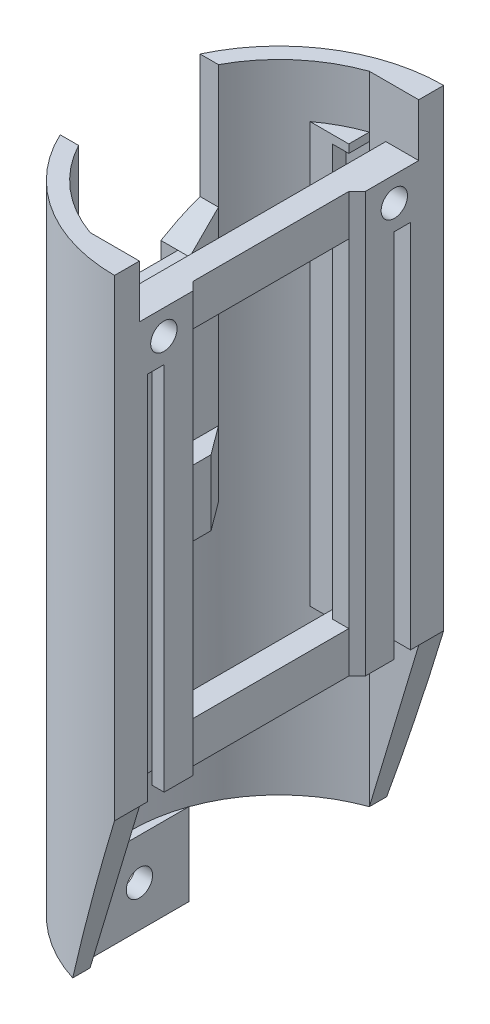
SolidWorks part; units mm, degrees
ref_plane "前视基准面" through (0, 0, 0) normal (0, 0, 1) x (1, 0, 0)
ref_plane "上视基准面" through (0, 0, 0) normal (0, 1, 0) x (1, 0, 0)
ref_plane "右视基准面" through (0, 0, 0) normal (1, 0, 0) x (0, 0, -1)
other "Configuration Table"
sketch "草图1" plane through (0, 0, 0) normal (0, 1, 0) x (1, 0, 0)
  line L0 (0, -473.638) -> (0, 23208.2609) construction
  line L1 (0, 0) -> (-4, 0) construction
  line L2 (0, 20) -> (0, -20)
  line L3 (-4, -17.5499) -> (-4, 17.5499)
  arc A0 (0, 20) -> (0, -20) centre (0, 0) ccw
  arc A1 (-4, 17.5499) -> (-4, -17.5499) centre (0, 0) ccw
  point P12 (-4, 0)
  dimension "D1" = 40
  dimension "D2" = 36
  dimension "D3" = 4
extrude "凸台-拉伸1" add sketch "草图1" along normal blind 70
sketch "草图3" plane through (0, 0, 0) normal (1, 0, 0) x (0, 0, -1)
  line L0 (-20, 0) -> (20, 0) construction
  line L1 (-16, 60) -> (16, 60) construction
  line L2 (-16, 60) -> (-16, 0) construction
  line L3 (-16, 0) -> (16, 0) construction
  line L4 (16, 60) -> (16, 0) construction
  line L5 (-20, 70) -> (20, 70) construction
  circle A0 centre (-14, 58) radius 2 construction
  circle A1 centre (14, 58) radius 2 construction
  circle A2 centre (-14, 58) radius 1
  circle A3 centre (14, 58) radius 1
  point P4 (0, 60)
  dimension "D4" = 4
  dimension "D5" = 4
  dimension "D6" = 2
  dimension "D7" = 2
  dimension "D1" = 0
  dimension "D2" = 10
  dimension "D3" = 32
extrude "切除-拉伸2" cut sketch "草图3" against normal up to surface (4 mm away) from surface up to face at (-4, 35, 0) starting at face at (0, 35, 0)
sketch "草图5" plane through (0, 0, 0) normal (0, 1, 0) x (1, 0, 0)
  line L0 (0, -1000) -> (0, 49000) construction
  line L1 (-1000, 0) -> (49000, 0) construction
  line L2 (-6, 16.9706) -> (6, 16.9706) construction
  line L3 (-6, -16.9706) -> (6, -16.9706) construction
  line L4 (0, 16.9706) -> (0, -16.9706)
  line L5 (0, -16.9706) -> (-4, -16.9706)
  line L6 (-4, -17.5499) -> (-4, 17.5499) construction
  line L7 (-4, -16.9706) -> (-4, 16.9706)
  line L8 (-4, 16.9706) -> (0, 16.9706)
  circle A0 centre (0, 0) radius 18 construction
  point P11 (0, 16.9706)
  dimension "D1" = 12
extrude "切除-拉伸4" cut sketch "草图5" against normal blind 9 from surface starting at face at (-10, 70, 0)
sketch "草图6" plane through (0, 0, 0) normal (0, 1, 0) x (1, 0, 0)
  line L0 (-4, 16.9706) -> (-6, 16.9706)
  line L1 (0, 16.9706) -> (0, 18)
  line L2 (-4, -16.9706) -> (-6, -16.9706)
  line L3 (0, -16.9706) -> (0, -18)
  line L4 (-4, 16.9706) -> (-4, -16.9706)
  line L5 (0, 16.9706) -> (-4, 16.9706)
  line L6 (0, -16.9706) -> (0, 16.9706)
  line L7 (-4, -16.9706) -> (0, -16.9706)
  line L9 (0, 16.9706) -> (-4, 16.9706)
  line L11 (-4, -16.9706) -> (0, -16.9706)
  arc A0 (0, 18) -> (-6, 16.9706) centre (0, 0) ccw
  arc A1 (-6, -16.9706) -> (0, -18) centre (0, 0) ccw
  dimension "D1" = 0
extrude "凸台-拉伸2" add sketch "草图6" against normal up to surface from surface up to face at (-10, 0, 0) starting at face at (-6.25, 70, 0)
sketch "草图7" plane through (0, 0, 0) normal (0, 1, 0) x (1, 0, 0)
  line L4 (-4, 16.9706) -> (-4, -16.9706)
  line L5 (0, 16.9706) -> (-4, 16.9706)
  line L6 (0, -16.9706) -> (0, 16.9706)
  line L7 (-4, -16.9706) -> (0, -16.9706)
  line L8 (-4, 16.9706) -> (-4, -16.9706)
  line L9 (0, 16.9706) -> (-4, 16.9706)
  line L10 (0, -16.9706) -> (0, 16.9706)
  line L11 (-4, -16.9706) -> (0, -16.9706)
  dimension "D1" = 0
extrude "切除-拉伸5" cut sketch "草图7" along normal blind 10
sketch "草图8" plane through (0, 0, 0) normal (0, 1, 0) x (1, 0, 0)
  line L0 (0, 16.9706) -> (0, -16.9706) construction
  line L1 (-6, 16.9706) -> (0, 16.9706)
  line L2 (-6, 16.9706) -> (-6, 14.4706)
  line L3 (-6, 14.4706) -> (0, 14.4706)
  line L4 (0, 16.9706) -> (0, 14.4706)
  line L6 (0, -16.9706) -> (-6, -16.9706)
  line L7 (0, -16.9706) -> (0, -14.4706)
  line L8 (0, -14.4706) -> (-6, -14.4706)
  line L9 (-6, -16.9706) -> (-6, -14.4706)
  dimension "D1" = 2.5
  dimension "D2" = 2.5
extrude "凸台-拉伸3" add sketch "草图8" against normal blind 1 from surface starting at face at (-2, 61, 0)
sketch "草图10" plane through (0, 0, 0) normal (0, 1, 0) x (1, 0, 0)
  line L0 (-6, 16.9706) -> (-6, 14.4706)
  line L1 (-6, 14.4706) -> (-10.7053, 14.4706)
  line L2 (-6, -14.4706) -> (-10.7053, -14.4706)
  line L3 (-6, -14.4706) -> (-6, -16.9706)
  arc A0 (-6, 16.9706) -> (-10.7053, 14.4706) centre (0, 0) ccw
  arc A1 (-10.7053, -14.4706) -> (-6, -16.9706) centre (0, 0) ccw
extrude "凸台-拉伸4" add sketch "草图10" along normal up to surface (70 mm away) from surface up to face at (-7.3333, 70, 0) starting at face at (-7.3333, 0, 0)
sketch "草图11" plane through (0, 0, 0) normal (0, 1, 0) x (1, 0, 0)
  line L0 (0, 16.9706) -> (0, -16.9706) construction
  line L1 (-6, 16.9706) -> (0, 16.9706)
  line L2 (-6, 16.9706) -> (-6, 14.4706)
  line L3 (-6, 14.4706) -> (0, 14.4706)
  line L4 (0, 16.9706) -> (0, 14.4706)
  line L5 (-6, 14.4706) -> (-10.7053, 14.4706) construction
  line L7 (-6, -14.4706) -> (0, -14.4706)
  line L8 (-6, -14.4706) -> (-6, -16.9706)
  line L9 (-6, -16.9706) -> (0, -16.9706)
  line L10 (0, -14.4706) -> (0, -16.9706)
  dimension "D1" = 0
extrude "凸台-拉伸5" add sketch "草图11" along normal up to surface (70 mm away) from surface up to face at (-7.2705, 70, 0) starting at face at (-4, 61, 0)
sketch "草图12" plane through (0, 0, 0) normal (0, 0, 1) x (1, 0, 0)
  line L1 (-6, 60) -> (-4, 60)
  line L2 (-6, 60) -> (-6, 61)
  line L3 (-6, 61) -> (-4, 61)
  line L4 (-4, 60) -> (-4, 61)
extrude "切除-拉伸6" cut sketch "草图12" against normal up to surface (16.9706 mm away) from surface up to face at (-3.3333, 23.3333, -16.9706) starting at face at (-3.3333, 23.3333, 16.9706)
sketch "草图14" plane through (0, 0, 0) normal (0, 1, 0) x (1, 0, 0)
  line L0 (-4, -14.4706) -> (-4, 14.4706) construction
  line L1 (-4, 10.4706) -> (-3, 10.4706)
  line L2 (-4, 10.4706) -> (-4, -10.4706)
  line L3 (-4, -10.4706) -> (-3, -10.4706)
  line L4 (-3, 10.4706) -> (-3, -10.4706)
  line L5 (-10.7053, -14.4706) -> (0, -14.4706) construction
  line L6 (-4, 14.4706) -> (0, 14.4706) construction
  line L7 (0, 14.4706) -> (0, -14.4706) construction
  line L8 (-1, 10.4706) -> (0, 10.4706)
  line L9 (-1, 10.4706) -> (-1, -10.4706)
  line L10 (-1, -10.4706) -> (0, -10.4706)
  line L11 (0, 10.4706) -> (0, -10.4706)
  line L12 (0, -14.4706) -> (-4, -14.4706) construction
  line L13 (0, 14.4706) -> (-10.7053, 14.4706) construction
  dimension "D1" = 1
  dimension "D2" = 4
  dimension "D3" = 4
  dimension "D4" = 1
  dimension "D5" = 4
  dimension "D6" = 4
extrude "切除-拉伸8" cut sketch "草图14" along normal up to surface (61 mm away) from surface up to face at (-2, 61, 0) starting at face at (-2, 10, 0)
sketch "草图15" plane through (0, 0, 0) normal (1, 0, 0) x (0, 0, -1)
  line L0 (10.4706, 61) -> (10.4706, 10) construction
  line L5 (-10.4706, 61) -> (-10.4706, 10) construction
  line L6 (10.4706, 61) -> (-10.4706, 61) construction
  line L7 (-10.4706, 10) -> (10.4706, 10) construction
  line L9 (-9.4706, 56) -> (9.4706, 56)
  line L10 (-9.4706, 56) -> (-9.4706, 15)
  line L11 (-9.4706, 15) -> (9.4706, 15)
  line L12 (9.4706, 56) -> (9.4706, 15)
  dimension "D1" = 1
  dimension "D2" = 1
  dimension "D3" = 5
  dimension "D4" = 5
extrude "切除-拉伸9" cut sketch "草图15" against normal up to surface (3 mm away) from surface up to face at (-3, 35.5, 0) starting at face at (-1, 35.5, 0)
sketch "草图17" plane through (0, 0, 0) normal (1, 0, 0) x (0, 0, -1)
  circle A0 centre (-14, 58) radius 1.6
  circle A1 centre (14, 58) radius 1.6
  dimension "D1" = 3.2
  dimension "D2" = 3.2
extrude "切除-拉伸10" cut sketch "草图17" against normal blind 2.5
sketch "草图20" plane through (0, 0, 0) normal (0, 1, 0) x (1, 0, 0)
  line L0 (-1, 10.4706) -> (0, 10.4706)
  line L1 (0, 14.4706) -> (0, 10.4706) construction
  line L2 (0, 10.4706) -> (-1, 10.4706) construction
  line L3 (0, 10.4706) -> (-1, 9.4706)
  line L4 (-1, 10.4706) -> (-1, -10.4706) construction
  line L5 (-1, 9.4706) -> (-1, 10.4706)
  line L6 (-4, 10.4706) -> (-3, 10.4706)
  line L7 (-3, 10.4706) -> (-3, 9.4706)
  line L8 (-3, -10.4706) -> (-3, 10.4706) construction
  line L9 (-3, 9.4706) -> (-4, 10.4706)
  line L10 (-4, -10.4706) -> (-3, -10.4706)
  line L11 (-3, -10.4706) -> (-3, -9.4706)
  line L12 (-3, -9.4706) -> (-4, -10.4706)
  line L13 (0, -10.4706) -> (-1, -10.4706)
  line L14 (-1, -10.4706) -> (0, -10.4706) construction
  line L15 (-1, -10.4706) -> (-1, -9.4706)
  line L16 (-1, -9.4706) -> (0, -10.4706)
  dimension "D1" = 1
  dimension "D2" = 1
  dimension "D3" = 1
  dimension "D4" = 1
  dimension "D5" = 1
extrude "凸台-拉伸11" add sketch "草图20" against normal up to surface (-10 mm away) from surface up to face at (-2, 10, 0) starting at face at (-2, 61, 0)
sketch "草图21" plane through (0, 0, 0) normal (0, 1, 0) x (1, 0, 0)
  line L0 (-4, 10.4706) -> (-4, -10.4706)
  line L1 (-4, -10.4706) -> (-3, -9.4706)
  line L2 (-3, -9.4706) -> (-3, 9.4706)
  line L3 (-3, 9.4706) -> (-4, 10.4706)
extrude "凸台-拉伸12" add sketch "草图21" against normal up to surface (-56 mm away) from surface up to face at (-2, 56, 0) starting at face at (-2, 61, 0)
sketch "草图22" plane through (0, 0, 0) normal (0, 1, 0) x (1, 0, 0)
  line L4 (-4, 10.4706) -> (-4, -10.4706)
  line L5 (-4, -10.4706) -> (-3, -9.4706)
  line L6 (-3, -9.4706) -> (-3, 9.4706)
  line L7 (-3, 9.4706) -> (-4, 10.4706)
  line L8 (-4, 10.4706) -> (-4, -10.4706)
  line L9 (-4, -10.4706) -> (-3, -9.4706)
  line L10 (-3, -9.4706) -> (-3, 9.4706)
  line L11 (-3, 9.4706) -> (-4, 10.4706)
  dimension "D1" = 0
extrude "凸台-拉伸13" add sketch "草图22" along normal up to surface (15 mm away) from surface up to face at (-2, 15, 0) starting at face at (-2, 10, 0)
sketch "草图23" plane through (0, 0, 0) normal (0, 0, 1) x (1, 0, 0)
  line L0 (-3, 56) -> (-1, 56) construction
  line L1 (-6, 61) -> (-8, 61)
  line L2 (-6, 61) -> (-6, 55)
  line L3 (-6, 55) -> (-8, 55)
  line L4 (-8, 61) -> (-8, 55)
  dimension "D1" = 1
  dimension "D2" = 2
extrude "切除-拉伸11" cut sketch "草图23" along normal up to surface (1.654 mm away) from surface up to face at (-14.3526, 35, 0) starting at face at (-5.3444, 46.1429, 14.4706)
sketch "草图24" plane through (0, 0, 0) normal (0, 0, 1) x (1, 0, 0)
  line L4 (-6, 61) -> (-8, 61)
  line L5 (-8, 61) -> (-8, 55)
  line L6 (-8, 55) -> (-6, 55)
  line L7 (-6, 55) -> (-6, 61)
  line L8 (-6, 61) -> (-8, 61)
  line L9 (-8, 61) -> (-8, 55)
  line L10 (-8, 55) -> (-6, 55)
  line L11 (-6, 55) -> (-6, 61)
  dimension "D1" = 0
extrude "切除-拉伸12" cut sketch "草图24" against normal up to surface (16.1245 mm away) up to face at (-14.3526, 35, 0)
sketch "草图25" plane through (0, 0, 0) normal (0, 1, 0) x (1, 0, 0)
  line L0 (-6, -16.9706) -> (-6, -14.4706)
  line L1 (-8, -14.4706) -> (-4, -14.4706) construction
  line L2 (-6, -14.4706) -> (-10.7053, -14.4706)
  line L3 (-10.7053, 14.4706) -> (-6, 14.4706)
  line L4 (-4, 14.4706) -> (-8, 14.4706) construction
  line L5 (-6, 14.4706) -> (-6, 16.9706)
  arc A0 (-10.7053, -14.4706) -> (-6, -16.9706) centre (0, 0) ccw
  arc A1 (-6, 16.9706) -> (-10.7053, 14.4706) centre (0, 0) ccw
extrude "切除-拉伸13" cut sketch "草图25" along normal up to surface (10 mm away) from surface up to face at (-1.25, 10, 0) starting at face at (-7.2705, 0, 0)
sketch "草图29" plane through (0, 0, 0) normal (0, 1, 0) x (1, 0, 0)
  line L0 (0, -16.9706) -> (0, -14.4706)
  line L1 (0, -14.4706) -> (-10.7053, -14.4706)
  line L2 (0, -16.9706) -> (-6, -16.9706)
  line L3 (-4, -16.9706) -> (-6, -16.9706)
  line L4 (0, -18) -> (0, -16.9706)
  line L5 (0, -16.9706) -> (-4, -16.9706)
  line L6 (-4, -16.9706) -> (-6, -16.9706) construction
  line L8 (0, -16.9706) -> (-4, -16.9706) construction
  line L9 (-6, 16.9706) -> (-4, 16.9706)
  line L10 (0, 16.9706) -> (0, 18)
  line L11 (-4, 16.9706) -> (0, 16.9706)
  line L12 (-6, 16.9706) -> (-4, 16.9706) construction
  line L14 (-4, 16.9706) -> (0, 16.9706) construction
  line L15 (-6, 16.9706) -> (0, 16.9706)
  line L16 (0, 16.9706) -> (0, 14.4706)
  line L17 (0, 14.4706) -> (-10.7053, 14.4706)
  arc A0 (-10.7053, -14.4706) -> (-6, -16.9706) centre (0, 0) ccw
  arc A1 (-6, -16.9706) -> (0, -18) centre (0, 0) ccw
  arc A3 (0, 18) -> (-6, 16.9706) centre (0, 0) ccw
  arc A5 (-6, 16.9706) -> (-10.7053, 14.4706) centre (0, 0) ccw
  dimension "D1" = 0
  dimension "D2" = 0
extrude "切除-拉伸18" cut sketch "草图29" against normal up to surface (-61 mm away) from surface up to face at (-1.25, 61, 0) starting at face at (-8.1175, 70, 0)
sketch "草图30" plane through (0, 0, 0) normal (0, 1, 0) x (1, 0, 0)
  line L0 (-8, 16.1245) -> (-8, 14.4706)
  line L1 (-8, 14.4706) -> (-4, 14.4706)
  line L2 (-4, -16.9706) -> (-4, 16.9706) construction
  line L3 (-4, 14.4706) -> (-4, 16.9706)
  line L4 (-6, 16.9706) -> (0, 16.9706) construction
  line L5 (-4, 16.9706) -> (-6, 16.9706)
  line L6 (-8, -16.1245) -> (-8, -14.4706)
  line L7 (-8, -14.4706) -> (-4, -14.4706)
  line L8 (-4, -14.4706) -> (-4, -16.9706)
  line L9 (-4, -16.9706) -> (-6, -16.9706)
  arc A0 (-6, 16.9706) -> (-8, 16.1245) centre (0, 0) ccw
  arc A1 (-8, -16.1245) -> (-6, -16.9706) centre (0, 0) ccw
extrude "凸台-拉伸16" add sketch "草图30" against normal blind 1 from surface starting at face at (-8.9139, 61, -15.0418)
sketch "草图31" plane through (0, 0, 0) normal (0, 1, 0) x (1, 0, 0)
  line L4 (0, -20) -> (0, -16.9706)
  line L5 (0, -16.9706) -> (-6, -16.9706)
  line L6 (-6, 16.9706) -> (0, 16.9706)
  line L7 (0, 16.9706) -> (0, 20)
  line L8 (0, -20) -> (0, -16.9706)
  line L9 (0, -16.9706) -> (-6, -16.9706)
  line L10 (-6, 16.9706) -> (0, 16.9706)
  line L11 (0, 16.9706) -> (0, 20)
  arc A2 (-6, 16.9706) -> (-6, -16.9706) centre (0, 0) ccw
  arc A3 (0, 20) -> (0, -20) centre (0, 0) ccw
  arc A4 (-6, 16.9706) -> (-6, -16.9706) centre (0, 0) ccw
  arc A5 (0, 20) -> (0, -20) centre (0, 0) ccw
  dimension "D1" = 0
extrude "凸台-拉伸17" add sketch "草图31" along normal blind 2.4 from surface starting at face at (-7.3333, 70, 0)
sketch "草图32" plane through (0, 0, 0) normal (0, 1, 0) x (1, 0, 0)
  line L4 (0, 16.9706) -> (0, 20)
  line L5 (0, -20) -> (0, -16.9706)
  line L6 (0, -16.9706) -> (-6, -16.9706)
  line L7 (-6, 16.9706) -> (0, 16.9706)
  line L8 (0, 16.9706) -> (0, 20)
  line L9 (0, -20) -> (0, -16.9706)
  line L10 (0, -16.9706) -> (-6, -16.9706)
  line L11 (-6, 16.9706) -> (0, 16.9706)
  arc A2 (0, 20) -> (0, -20) centre (0, 0) ccw
  arc A3 (-6, 16.9706) -> (-6, -16.9706) centre (0, 0) ccw
  arc A4 (0, 20) -> (0, -20) centre (0, 0) ccw
  arc A5 (-6, 16.9706) -> (-6, -16.9706) centre (0, 0) ccw
  dimension "D1" = 0
extrude "切除-拉伸19" cut sketch "草图32" against normal blind 5 from surface starting at face at (-7.3333, 72.4, 0)
sketch "草图33" plane through (0, 0, 0) normal (0, 1, 0) x (1, 0, 0)
  line L0 (-1000, 0) -> (49000, 0) construction
  line L1 (-17.2916, -5) -> (-17.2916, 5)
  line L2 (-17.2916, 5) -> (-19.3649, 5)
  line L3 (-17.2916, -5) -> (-19.3649, -5)
  arc A0 (-17.2916, 5) -> (-17.2916, -5) centre (0, 0) ccw construction
  arc A1 (-19.3649, 5) -> (-19.3649, -5) centre (0, 0) ccw
  point P11 (-17.2916, 0)
  dimension "D1" = 10
extrude "切除-拉伸20" cut sketch "草图33" against normal blind 45 from surface starting at face at (-7.3333, 67.4, 0)
sketch "草图39" plane through (0, 0, 0) normal (0, 1, 0) x (1, 0, 0)
  line L0 (-20, 0) -> (-15.8666, 0) construction
  line L1 (-15.8666, -8.5) -> (-15.8666, 8.5)
  line L2 (-15.8666, 8.5) -> (-18.1039, 8.5)
  line L3 (-15.8666, -8.5) -> (-18.1039, -8.5)
  arc A0 (-18.1039, 8.5) -> (-18.1039, -8.5) centre (0, 0) ccw
  arc A1 (-15.8666, 8.5) -> (-15.8666, -8.5) centre (0, 0) ccw construction
  point P11 (-15.8666, 0)
  dimension "D1" = 17
extrude "切除-拉伸22" cut sketch "草图39" against normal blind 15 from surface contours L2 A0 L3 L1 region at (-17.6683, 0, 0) starting at face at (-9.3339, 67.4, 13.7237)
sketch "草图40" plane through (0, 0, 0) normal (1, 0, 0) x (0, 0, -1)
  line L0 (-5, 52.4) -> (-8.5, 52.4)
  line L1 (-8.5, 52.4) -> (-5, 48.9)
  line L2 (-5, 22.4) -> (-5, 52.4) construction
  line L3 (-5, 48.9) -> (-5, 52.4)
  line L4 (8.5, 52.4) -> (5, 52.4)
  line L5 (5, 52.4) -> (5, 48.9)
  line L6 (5, 22.4) -> (5, 52.4) construction
  line L7 (5, 48.9) -> (8.5, 52.4)
  dimension "D1" = 3.5
  dimension "D2" = 3.5
extrude "切除-拉伸25" cut sketch "草图40" against normal through all
sketch "草图41" plane through (0, 0, 0) normal (0, 1, 0) x (1, 0, 0)
  line L0 (-1000, 0) -> (49000, 0) construction
  line L1 (-15.8666, 8.5) -> (-15.8666, -8.5)
  line L2 (-17.2916, 5) -> (-17.2916, -5)
  arc A0 (-17.2916, -5) -> (-15.8666, -8.5) centre (0, 0) ccw
  arc A1 (-15.8666, 8.5) -> (-17.2916, 5) centre (0, 0) ccw
extrude "凸台-拉伸24" add sketch "草图41" along normal up to vertex (48.9 mm away) from surface up to point (-19.3649, 48.9, -5) starting at face at (-18.6641, 22.4, 0)
sketch "草图42" plane through (0, 0, 0) normal (1, 0, 0) x (0, 0, -1)
  line L0 (-8.5, 52.4) -> (-8.5, 48.9)
  line L1 (-8.5, 48.9) -> (-5, 48.9)
  line L2 (-5, 48.9) -> (-8.5, 52.4)
  line L3 (8.5, 52.4) -> (8.5, 48.9)
  line L4 (8.5, 48.9) -> (5, 48.9)
  line L5 (5, 48.9) -> (8.5, 52.4)
extrude "凸台-拉伸25" add sketch "草图42" against normal up to surface (2.2372 mm away) from surface up to face at (-14.5014, 43.0882, 0) starting at face at (-15.8666, 35.65, 0)
sketch "草图43" plane through (0, 0, 0) normal (0, 1, 0) x (1, 0, 0)
  line L0 (-15.8666, 8.5) -> (-15.8666, -8.5)
  arc A0 (-15.8666, 8.5) -> (-15.8666, -8.5) centre (0, 0) ccw
extrude "凸台-拉伸26" add sketch "草图43" against normal blind 1 from surface starting at face at (-16.6252, 22.4, 0)
sketch "草图44" plane through (0, 0, 0) normal (0, 1, 0) x (1, 0, 0)
  line L0 (-1000, 0) -> (49000, 0) construction
  line L1 (-15.8666, 0) -> (-13.2666, 0) construction
  line L2 (-15.8666, 5) -> (-15.8666, -5) construction
  line L3 (-13.2666, -5) -> (-13.2666, 5)
  line L4 (-13.2666, 5) -> (-15.8666, 8.5)
  line L5 (-13.2666, -5) -> (-15.8666, -8.5)
  line L6 (-15.8666, 8.5) -> (-15.8666, -8.5)
  circle A1 centre (0, 0) radius 18 construction
  point P12 (-13.2666, 0)
  dimension "D1" = 2.6
  dimension "D2" = 10
extrude "凸台-拉伸27" add sketch "草图44" along normal blind 8 from surface starting at face at (-16.9333, 21.4, 0)
sketch "草图45" plane through (0, 0, 0) normal (1, 0, 0) x (0, 0, -1)
  line L0 (0, 67.4) -> (0, 21.4) construction
  line L2 (5, 22.4) -> (-5, 22.4) construction
  circle A0 centre (0, 26.4) radius 1
  dimension "D1" = 2
  dimension "D2" = 4
extrude "切除-拉伸26" cut sketch "草图45" along normal up to surface (-13.2666 mm away) from surface up to face at (-13.2666, 25.4, 0) starting at face at (-17.2916, 35.65, 0)
sketch "草图46" plane through (0, 0, 0) normal (0, 1, 0) x (1, 0, 0)
  line L0 (-15.8666, 5) -> (-15.8666, -5) construction
  line L1 (-15.8666, 2) -> (-14.2666, 2)
  line L2 (-15.8666, 2) -> (-15.8666, -2)
  line L3 (-15.8666, -2) -> (-14.2666, -2)
  line L4 (-14.2666, 2) -> (-14.2666, -2)
  line L5 (-17.2916, -5) -> (-17.2916, 5) construction
  point P8 (-17.2916, 0)
  point P9 (-15.8666, 0)
  dimension "D1" = 4
  dimension "D2" = 1.6
extrude "切除-拉伸27" cut sketch "草图46" along normal blind 5 from surface starting at face at (-15.1, 21.4, 0)
sketch "草图47" plane through (0, 0, 0) normal (1, 0, 0) x (0, 0, -1)
  line L1 (0, 24.0906) -> (2, 25.2453)
  line L2 (2, 25.2453) -> (2, 27.5547)
  line L3 (2, 27.5547) -> (0, 28.7094)
  line L4 (0, 28.7094) -> (-2, 27.5547)
  line L5 (-2, 27.5547) -> (-2, 25.2453)
  line L6 (-2, 25.2453) -> (0, 24.0906)
  circle A0 centre (0, 26.4) radius 2 construction
  dimension "D1" = 4
extrude "切除-拉伸28" cut sketch "草图47" against normal up to surface (15.8666 mm away) from surface up to face at (-15.8666, 24.5667, 0) starting at face at (-14.2666, 24.5667, 0)
sketch "草图48" plane through (0, 0, 0) normal (1, 0, 0) x (0, 0, -1)
  line L0 (5, 22.4) -> (3, 22.4)
  line L1 (5, 22.4) -> (-5, 22.4) construction
  line L2 (3, 22.4) -> (5, 24.4)
  line L3 (5, 22.4) -> (5, 48.9) construction
  line L4 (5, 24.4) -> (5, 22.4)
  line L5 (-5, 22.4) -> (-5, 24.4)
  line L6 (-5, 22.4) -> (-5, 48.9) construction
  line L7 (-5, 24.4) -> (-3, 22.4)
  line L8 (-3, 22.4) -> (-5, 22.4)
  dimension "D1" = 2
  dimension "D2" = 2
  dimension "D3" = 2
  dimension "D4" = 2
extrude "凸台-拉伸28" add sketch "草图48" against normal up to surface (2.0733 mm away) from surface up to face at (-14.5014, 43.0882, 0) starting at face at (-17.2916, 26.4, 1)
sketch "草图49" plane through (0, 0, 0) normal (0, 1, 0) x (1, 0, 0)
  line L1 (-6, -16.9706) -> (-4, -16.9706)
  line L2 (-6, -16.9706) -> (-6, 16.9706)
  line L3 (-6, 16.9706) -> (-4, 16.9706)
  line L4 (-4, -16.9706) -> (-4, 16.9706)
extrude "切除-拉伸29" cut sketch "草图49" along normal through all
sketch "草图50" plane through (0, 0, 0) normal (0, 1, 0) x (1, 0, 0)
  line L0 (0, 16.9706) -> (0, 15.9706) construction
  line L1 (0, 16.9706) -> (0, 10.4706) construction
  line L2 (0, 15.9706) -> (-3, 15.9706)
  line L3 (-3, 15.9706) -> (-3, 11.9706)
  line L4 (-3, 11.9706) -> (-1.5, 11.9706)
  line L5 (-1.5, 11.9706) -> (-1.5, 13.9706)
  line L6 (-1.5, 13.9706) -> (0, 13.9706)
  line L7 (-1000, 0) -> (49000, 0) construction
  line L8 (-1.5, -13.9706) -> (0, -13.9706)
  line L9 (-1.5, -11.9706) -> (-1.5, -13.9706)
  line L10 (-3, -11.9706) -> (-1.5, -11.9706)
  line L11 (-3, -15.9706) -> (-3, -11.9706)
  line L12 (0, -15.9706) -> (-3, -15.9706)
  line L13 (0, -16.9706) -> (0, -15.9706) construction
  line L14 (0, 15.9706) -> (0, 13.9706)
  line L15 (0, -13.9706) -> (0, -15.9706)
  dimension "D1" = 1
  dimension "D2" = 3
  dimension "D3" = 1.5
  dimension "D4" = 2
  dimension "D5" = 2
extrude "切除-拉伸30" cut sketch "草图50" along normal blind 45 from surface starting at face at (-1.25, 10, 0)
sketch "草图51" plane through (0, 0, 0) normal (0, 1, 0) x (1, 0, 0)
  line L0 (0, -11.9706) -> (3, -11.9706)
  line L1 (0, -13.9706) -> (0, -10.4706) construction
  line L2 (3, -11.9706) -> (3, -14.9706)
  line L3 (3, -14.9706) -> (0, -14.9706) construction
  line L4 (1.5, -14.9706) -> (1.5, -13.9706)
  line L5 (1.5, -13.9706) -> (0, -13.9706)
  line L6 (-3, -11.9706) -> (-1.5, -11.9706) construction
  line L7 (1.5, -14.9706) -> (3, -14.9706)
  line L8 (0, -13.9706) -> (0, -11.9706)
  line L9 (-1000, 0) -> (49000, 0) construction
  line L10 (3, 14.9706) -> (0, 14.9706) construction
  line L11 (0, 13.9706) -> (0, 11.9706)
  line L12 (1.5, 14.9706) -> (3, 14.9706)
  line L13 (1.5, 13.9706) -> (0, 13.9706)
  line L14 (1.5, 14.9706) -> (1.5, 13.9706)
  line L15 (3, 11.9706) -> (3, 14.9706)
  line L16 (0, 11.9706) -> (3, 11.9706)
  dimension "D1" = 3
  dimension "D2" = 3
  dimension "D3" = 3
extrude "凸台-拉伸29" add sketch "草图51" along normal blind 45 from surface starting at face at (-1.4, 10, 0)
sketch "草图52" plane through (0, 0, 0) normal (0, 1, 0) x (1, 0, 0)
  line L4 (0, -16.9706) -> (-6, -16.9706)
  line L5 (0, -20) -> (0, -16.9706)
  line L6 (0, 16.9706) -> (0, 20)
  line L7 (-6, 16.9706) -> (0, 16.9706)
  line L8 (0, -16.9706) -> (-6, -16.9706)
  line L9 (0, -20) -> (0, -16.9706)
  line L10 (0, 16.9706) -> (0, 20)
  line L11 (-6, 16.9706) -> (0, 16.9706)
  arc A2 (-6, 16.9706) -> (-6, -16.9706) centre (0, 0) ccw
  arc A3 (0, 20) -> (0, -20) centre (0, 0) ccw
  arc A4 (-6, 16.9706) -> (-6, -16.9706) centre (0, 0) ccw
  arc A5 (0, 20) -> (0, -20) centre (0, 0) ccw
  dimension "D1" = 0
extrude "凸台-拉伸30" add sketch "草图52" against normal blind 10
sketch "草图58" plane through (0, 0, 0) normal (0, 1, 0) x (1, 0, 0)
  line L0 (1.5, -13.9706) -> (1.5, -14.9706) construction
  line L1 (1.5, -14.9706) -> (3, -14.9706) construction
  line L2 (3, -14.9706) -> (3, -11.9706) construction
  line L3 (3, -11.9706) -> (0, -11.9706) construction
  line L4 (0, -11.9706) -> (0, -13.9706) construction
  line L5 (0, -13.9706) -> (1.5, -13.9706) construction
  line L6 (1.5, 13.9706) -> (0, 13.9706) construction
  line L7 (0, 13.9706) -> (0, 11.9706) construction
  line L8 (0, 11.9706) -> (3, 11.9706) construction
  line L9 (3, 11.9706) -> (3, 14.9706) construction
  line L10 (3, 14.9706) -> (1.5, 14.9706) construction
  line L11 (1.5, 14.9706) -> (1.5, 13.9706) construction
  line L12 (1.5, -13.9706) -> (1.5, -14.9706)
  line L13 (1.5, -14.9706) -> (3, -14.9706)
  line L14 (3, -14.9706) -> (3, -11.9706)
  line L15 (3, -11.9706) -> (0, -11.9706)
  line L16 (0, -11.9706) -> (0, -13.9706)
  line L17 (0, -13.9706) -> (1.5, -13.9706)
  line L18 (1.5, 13.9706) -> (0, 13.9706)
  line L19 (0, 13.9706) -> (0, 11.9706)
  line L20 (0, 11.9706) -> (3, 11.9706)
  line L21 (3, 11.9706) -> (3, 14.9706)
  line L22 (3, 14.9706) -> (1.5, 14.9706)
  line L23 (1.5, 14.9706) -> (1.5, 13.9706)
extrude "切除-拉伸34" cut sketch "草图58" along normal up to surface (55 mm away) from surface up to face at (1.5, 55, 13.6372) starting at face at (-0.3571, 10, 0)
sketch "草图60" plane through (0, 0, 0) normal (0, 0, 1) x (1, 0, 0)
  line L0 (0, 10) -> (-6, -10)
  line L1 (-6, -10) -> (0, -10)
  line L2 (0, -10) -> (0, 10)
extrude "切除-拉伸35" cut sketch "草图60" against normal through all and the other way through all
sketch "草图61" plane through (0, 0, 0) normal (0, 1, 0) x (1, 0, 0)
  line L0 (-1000, 0) -> (49000, 0) construction
  line L1 (-16.9706, 6) -> (-16.9706, -6)
  line L2 (-16.9706, -6) -> (-19.0788, -6)
  line L3 (-16.9706, 6) -> (-19.0788, 6)
  arc A0 (-19.0788, 6) -> (-19.0788, -6) centre (0, 0) ccw
  arc A1 (-16.9706, 6) -> (-16.9706, -6) centre (0, 0) ccw construction
  point P11 (-16.9706, 0)
  dimension "D1" = 12
extrude "凸台-拉伸32" add sketch "草图61" against normal blind 10 from surface starting at face at (-12.5, -10, 0)
sketch "草图62" plane through (0, 0, 0) normal (0, 1, 0) x (1, 0, 0)
  line L0 (-19.0788, -6) -> (-19.0788, 6)
  arc A0 (-19.0788, 6) -> (-19.0788, -6) centre (0, 0) ccw construction
  arc A1 (-19.0788, 6) -> (-19.0788, -6) centre (0, 0) ccw
extrude "切除-拉伸36" cut sketch "草图62" against normal blind 10 from surface starting at face at (-12.7237, -10, 12.7237)
sketch "草图63" plane through (0, 0, 0) normal (1, 0, 0) x (0, 0, -1)
  line L0 (-6, -20) -> (6, -20) construction
  line L1 (6, -20) -> (6, -10) construction
  circle A0 centre (0, -15) radius 1.6
  dimension "D1" = 3.2
  dimension "D2" = 5
  dimension "D3" = 6
extrude "切除-拉伸37" cut sketch "草图63" against normal through all
sketch "草图65" plane through (0, 0, 0) normal (1, 0, 0) x (0, 0, -1)
  line L0 (-6, -10) -> (6, -10)
  line L3 (6, -10) -> (6, -14)
  line L11 (6, -20) -> (6, -10) construction
  line L12 (6, -14) -> (3, -11)
  line L13 (3, -11) -> (-3, -11)
  line L14 (-3, -11) -> (-6, -14)
  line L15 (-6, -20) -> (-6, -10) construction
  line L16 (-6, -14) -> (-6, -10)
  point P14 (12.0034, -11.9994)
  dimension "D1" = 4
  dimension "D2" = 6
  dimension "D3" = 3
  dimension "D4" = 4
  dimension "D5" = 3
extrude "凸台-拉伸33" add sketch "草图65" against normal up to surface from surface up to face at (-13.7534, 30.313, 0) starting at face at (-19.0788, -15, -1.6)
